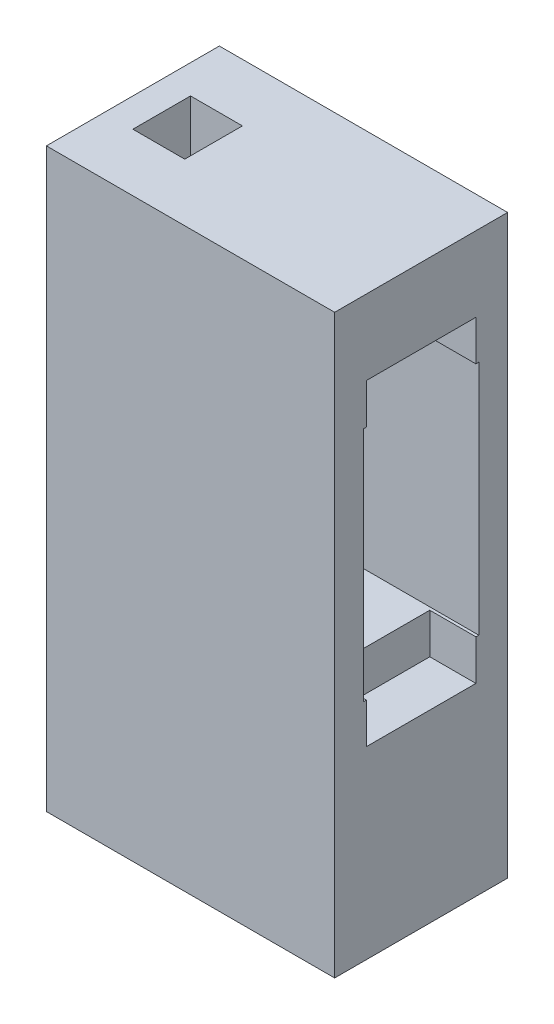
SolidWorks part; units mm, degrees
ref_plane "前基準面" through (0, 0, 0) normal (0, 0, 1) x (1, 0, 0)
ref_plane "上基準面" through (0, 0, 0) normal (0, 1, 0) x (1, 0, 0)
ref_plane "右基準面" through (0, 0, 0) normal (1, 0, 0) x (0, 0, -1)
sketch "草圖3" plane through (0, 0, 0) normal (0, 1, 0) x (1, 0, 0)
  line L1 (-17, 18) -> (33, 18)
  line L2 (-17, 18) -> (-17, -12)
  line L3 (-17, -12) -> (33, -12)
  line L4 (33, 18) -> (33, -12)
  dimension "D1" = 50
  dimension "D2" = 30
extrude "填料-伸長1" add sketch "草圖3" along normal blind 100
sketch "草圖4" plane through (33, 0, 0) normal (1, 0, 0) x (0, 0, -1)
  line L0 (-12, 100) -> (18, 100) construction
  line L1 (-7, 80) -> (13, 80)
  line L2 (-7, 80) -> (-7, 39)
  line L3 (-7, 39) -> (13, 39)
  line L4 (13, 80) -> (13, 39)
  line L5 (-12, 100) -> (-12, 0) construction
  dimension "D1" = 41
  dimension "D2" = 20
  dimension "D3" = 20
  dimension "D4" = 5
extrude "除料-伸長1" cut sketch "草圖4" against normal blind 37
sketch "草圖5" plane through (33, 0, 0) normal (1, 0, 0) x (0, 0, -1)
  line L0 (13, 80) -> (-7, 80) construction
  line L1 (-6.5, 80) -> (12.5, 80)
  line L2 (-6.5, 80) -> (-6.5, 87)
  line L3 (-6.5, 87) -> (12.5, 87)
  line L4 (12.5, 80) -> (12.5, 87)
  line L5 (-12, 100) -> (-12, 0) construction
  line L6 (-7, 39) -> (13, 39) construction
  line L7 (-6.5, 39) -> (12.5, 39)
  line L8 (-6.5, 39) -> (-6.5, 32)
  line L9 (-6.5, 32) -> (12.5, 32)
  line L10 (12.5, 39) -> (12.5, 32)
  dimension "D1" = 7
  dimension "D2" = 19
  dimension "D3" = 5.5
  dimension "D4" = 7
extrude "除料-伸長2" cut sketch "草圖5" against normal blind 8
sketch "草圖6" plane through (25, 0, 0) normal (1, 0, 0) x (0, 0, -1)
  line L0 (-6.5, 80) -> (12.5, 80) construction
  line L1 (-0.5, 80) -> (6.5, 80)
  line L2 (-0.5, 80) -> (-0.5, 87)
  line L3 (-0.5, 87) -> (6.5, 87)
  line L4 (6.5, 80) -> (6.5, 87)
  line L5 (-6.5, 87) -> (-6.5, 80) construction
  dimension "D1" = 7
  dimension "D2" = 7
  dimension "D3" = 6
extrude "除料-伸長3" cut sketch "草圖6" against normal blind 29
sketch "草圖8" plane through (0, 100, 0) normal (0, 1, 0) x (1, 0, 0)
  line L0 (-17, 18) -> (-17, -12) construction
  line L1 (-12, 8) -> (-3, 8)
  line L2 (-12, 8) -> (-12, -2)
  line L3 (-12, -2) -> (-3, -2)
  line L4 (-3, 8) -> (-3, -2)
  line L5 (-17, -12) -> (33, -12) construction
  dimension "D1" = 10
  dimension "D2" = 9
  dimension "D3" = 5
  dimension "D4" = 10
extrude "除料-伸長4" cut sketch "草圖8" against normal blind 61
sketch "草圖9" plane through (-17, 0, 0) normal (-1, 0, 0) x (0, 0, 1)
  line L0 (12, 100) -> (12, 0) construction
  line L1 (-8, 39) -> (2, 39)
  line L2 (-8, 39) -> (-8, 49)
  line L3 (-8, 49) -> (2, 49)
  line L4 (2, 39) -> (2, 49)
  line L6 (-18, 100) -> (12, 100) construction
  dimension "D1" = 10
  dimension "D2" = 10
  dimension "D3" = 10
  dimension "D4" = 51
extrude "除料-伸長5" cut sketch "草圖9" against normal blind 5
fillet "圓角1" radius 5 1 edges at (-12, 49, -3)
sketch "草圖10" plane through (-17, 0, 0) normal (-1, 0, 0) x (0, 0, 1)
  line L0 (-18, 100) -> (12, 100) construction
  circle A0 centre (-2.0385, 71) radius 3
  dimension "D1" = 6
  dimension "D2" = 29
extrude "除料-伸長6" cut sketch "草圖10" against normal blind 5
